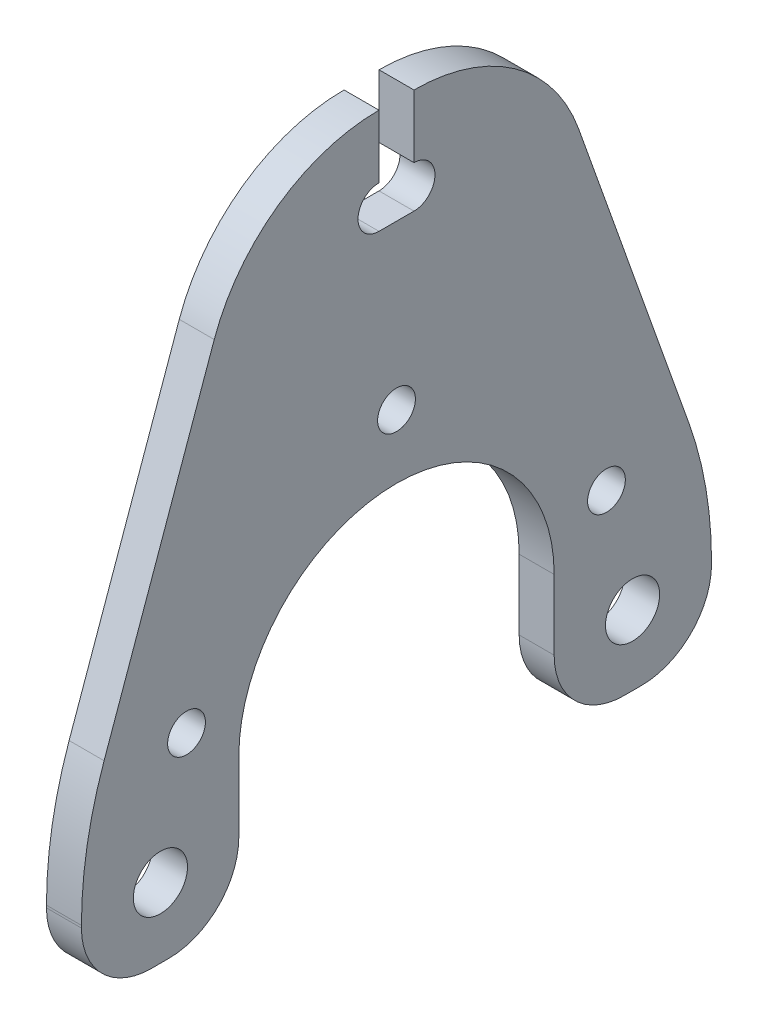
SolidWorks part; units mm, degrees
material "6061 Alloy"
ref_plane "Front Plane" through (0, 0, 0) normal (0, 0, 1) x (1, 0, 0)
ref_plane "Top Plane" through (0, 0, 0) normal (0, 1, 0) x (1, 0, 0)
ref_plane "Right Plane" through (0, 0, 0) normal (1, 0, 0) x (0, 0, -1)
sketch "Sketch1" plane through (0, 0, 0) normal (1, 0, 0) x (0, 0, -1)
  line L0 (1.5875, 44.45) -> (1.5875, 34.925)
  line L1 (1.5875, 34.925) -> (-1.5875, 34.925)
  line L2 (0, 0) -> (0, 73.524) construction
  line L3 (-1.5875, 44.45) -> (-1.5875, 34.925)
  line L4 (21.4566, -6.35) -> (-21.4566, -6.35) construction
  line L5 (16.5446, 33.895) -> (28.6004, 0)
  line L6 (-16.5446, 33.895) -> (-28.6004, 0)
  line L7 (28.6004, 0) -> (28.6004, -12.7)
  line L8 (28.6004, -12.7) -> (14.3129, -12.7)
  line L9 (14.3129, -12.7) -> (14.3129, 0)
  line L10 (-14.3129, 0) -> (-14.3129, -12.7)
  line L11 (-14.3129, -12.7) -> (-28.6004, -12.7)
  line L12 (-28.6004, -12.7) -> (-28.6004, 0)
  arc A0 (14.3129, 0) -> (-14.3129, 0) centre (0, 0) ccw
  arc A5 (16.5446, 33.895) -> (1.5875, 44.45) centre (1.5875, 28.575) ccw
  arc A10 (-16.5446, 33.895) -> (-1.5875, 44.45) centre (-1.5875, 28.575) cw
  circle A11 centre (21.4566, -6.35) radius 2.5797 construction
  circle A12 centre (-21.4566, -6.35) radius 2.5797 construction
  point P1 (0, -6.35)
  point P9 (21.4566, -12.7)
  point P18 (0, 34.925)
  dimension "D1" = 28.6258
  dimension "D3" = 57.15
  dimension "D4" = 15.875
  dimension "D5" = 12.7
  dimension "D6" = 42.9133
  dimension "D7" = 14.2875
  dimension "D9" = 5.1594
  dimension "D2" = 3.175
  dimension "D10" = 6.35
  dimension "D12" = 9.525
extrude "Boss-Extrude1" add sketch "Sketch1" along normal blind 3.175
hole_wizard "#10 (0.1935) Diameter Hole1" positions "Sketch2" profile "Sketch3" hole size "#10" standard "ANSI Inch"
sketch "Sketch2" plane through (0, 0, 0) normal (-1, 0, 0) x (0, 0, 1)
  line L2 (-21.4312, -6.35) -> (21.4312, -6.35) construction
  point P0 (-21.4312, -6.35)
  point P2 (21.4312, -6.35)
  point P29 (0, -6.35)
  dimension "D1" = 42.8625
  dimension "D2" = 6.35
sketch "Sketch3" plane through (0, -6.35, -21.4312) normal (0, 1, 0) x (0, 0, 1)
  line L0 (0, 0) -> (0, 20.4786)
  line L1 (0, 20.4786) -> (2.4574, 19.002)
  line L2 (2.4574, 19.002) -> (2.4574, 0)
  line L5 (2.4574, 0) -> (0, 0)
  line L10 (0, 20.4786) -> (-2.4574, 19.002) construction
  line L11 (0, -6.35) -> (0, 107.95) construction
  dimension "Hole Dia." = 4.9149
  dimension "Hole Depth" = 19.002
  dimension "Drill Angle" = 118
sketch "Sketch4" plane through (3.175, 0, 0) normal (1, 0, 0) x (0, 0, -1)
  circle A6 centre (0, 20.0978) radius 1.7145 construction
  circle A7 centre (0, 20.0978) radius 1.7145
  circle A8 centre (-19.0616, 4.2227) radius 1.7145 construction
  circle A9 centre (-19.0616, 4.2227) radius 1.7145
  circle A10 centre (19.0616, 4.2228) radius 1.7145 construction
  circle A11 centre (19.0616, 4.2228) radius 1.7145
extrude "Cut-Extrude1" cut sketch "Sketch4" against normal through all
fillet "Fillet2" radius 35.56 2 edges at (1.5875, 0, 28.6004) (1.5875, 0, -28.6004)
fillet "Fillet1" radius 6.35 4 edges at (1.5875, -12.7, -28.6004) (1.5875, -12.7, -14.3129) (1.5875, -12.7, 28.6004) (1.5875, -12.7, 14.3129)
sketch "Sketch5" [suppressed] plane through (3.175, 0, 0) normal (1, 0, 0) x (0, 0, -1)
  line L0 (-16.5481, 33.885) -> (-26.5267, 5.7708) construction
  line L1 (-4.7625, 44.1293) -> (-25.9843, 44.1293)
  line L2 (-25.9843, 44.1293) -> (-25.9843, 7.2993)
  line L3 (-1.5875, 34.925) -> (-1.5875, 44.45) construction
  line L4 (-4.7625, 44.1293) -> (-4.7625, 41.2634)
  line L5 (-1.5875, 34.925) -> (-1.5875, 44.45) construction
  arc A1 (-1.5875, 44.45) -> (-16.5481, 33.885) centre (-1.5875, 28.575) ccw construction
  arc A3 (-11.1125, 27.0644) -> (-25.9843, 7.2993) centre (31.2208, -20.2657) ccw
  arc A4 (-4.7625, 41.2634) -> (-11.1125, 27.0644) centre (-23.8125, 41.2634) cw
  dimension "D1" = 3.175
  dimension "D2" = 19.05
  dimension "D4" = 63.5
  dimension "D3" = 9.525
  dimension "D5" = 36.83
extrude "Cut-Extrude2" [suppressed] cut sketch "Sketch5" against normal through all
sketch "Sketch6" plane through (3.175, 0, 0) normal (1, 0, 0) x (0, 0, -1)
  line L0 (-1.5875, 34.925) -> (-1.5875, 44.45) construction
  line L1 (1.5875, 44.45) -> (1.5875, 34.925) construction
  line L2 (1.5875, 34.925) -> (-1.5875, 34.925) construction
  line L3 (-1.5875, 38.735) -> (1.5875, 38.735)
  line L4 (-1.5875, 34.925) -> (1.5875, 34.925)
  arc A0 (-1.5875, 38.735) -> (-1.5875, 34.925) centre (-1.5875, 36.83) ccw
  arc A1 (1.5875, 34.925) -> (1.5875, 38.735) centre (1.5875, 36.83) ccw
  dimension "D1" = 3.81
extrude "Cut-Extrude3" cut sketch "Sketch6" against normal through all
sketch "Sketch7" [suppressed] plane through (3.175, 0, 0) normal (1, 0, 0) x (0, 0, -1)
  line L0 (1.5875, 44.45) -> (1.5875, 34.925) construction
  line L1 (1.5875, 34.925) -> (-1.5875, 34.925) construction
  circle A0 centre (1.5875, 36.83) radius 1.905
  dimension "D1" = 3.81
extrude "Cut-Extrude4" [suppressed] cut sketch "Sketch7" against normal through all
